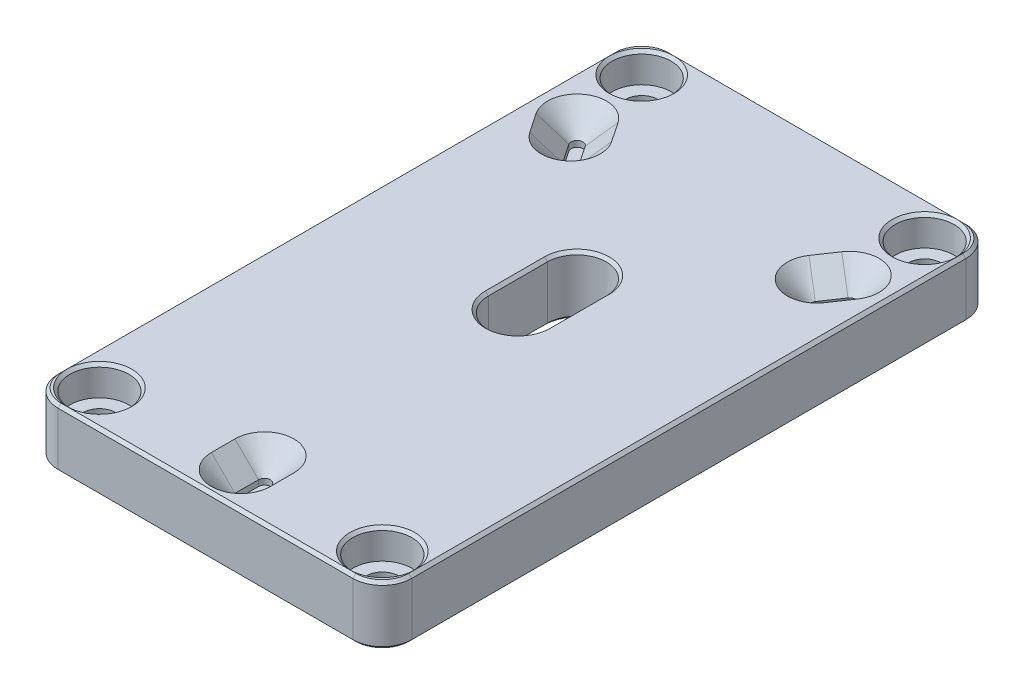
SolidWorks part; units mm, degrees
ref_plane "Front Plane" through (0, 0, 0) normal (0, 0, 1) x (1, 0, 0)
ref_plane "Top Plane" through (0, 0, 0) normal (0, 1, 0) x (1, 0, 0)
ref_plane "Right Plane" through (0, 0, 0) normal (1, 0, 0) x (0, 0, -1)
sketch "Sketch1" plane through (0, 0, 0) normal (0, 1, 0) x (1, 0, 0)
  line L1 (-30, 52) -> (30, 52)
  line L2 (-30, 52) -> (-30, -52)
  line L3 (-30, -52) -> (30, -52)
  line L4 (30, 52) -> (30, -52)
  line L5 (-30, 52) -> (30, -52) construction
  line L6 (-30, -52) -> (30, 52) construction
  point P0 (0, 0)
  dimension "D1" = 60
  dimension "D2" = 104
extrude "Boss-Extrude1" add sketch "Sketch1" along normal blind 10
sketch "Sketch10" plane through (0, 10, 0) normal (0, 1, 0) x (1, 0, 0)
  circle A0 centre (0, -44) radius 2.75 construction
  circle A1 centre (-22, 32.5) radius 2.75 construction
  circle A2 centre (22, 32.5) radius 2.75 construction
  circle A3 centre (0, -44) radius 2.75
  circle A4 centre (-22, 32.5) radius 2.75
  circle A5 centre (22, 32.5) radius 2.75
  circle A6 centre (0, 34) radius 15 construction
  circle A7 centre (0, -21.5) radius 15 construction
  circle A8 centre (0, 34) radius 15
  circle A9 centre (0, -21.5) radius 15
  circle A10 centre (0, 11) radius 1.85 construction
  circle A11 centre (0, 1) radius 1.85 construction
  circle A12 centre (0, 11) radius 1.85
  circle A13 centre (0, 1) radius 1.85
sketch "Sketch3" plane through (0, 10, 0) normal (0, 1, 0) x (1, 0, 0)
  line L0 (0, 0) -> (22, 32.5) construction
  line L1 (0, 0) -> (-22, 32.5) construction
  line L5 (0, 0) -> (0, -44) construction
  line L6 (-23.1211, 34.1562) -> (-20.8789, 30.8438) construction
  line L7 (-22.293, 34.7168) -> (-20.0508, 31.4043)
  line L8 (-23.9492, 33.5957) -> (-21.707, 30.2832)
  line L9 (23.1211, 34.1562) -> (20.8789, 30.8438) construction
  line L10 (23.9492, 33.5957) -> (21.707, 30.2832)
  line L11 (22.293, 34.7168) -> (20.0508, 31.4043)
  line L12 (0, -46) -> (0, -42) construction
  line L13 (-1, -46) -> (-1, -42)
  line L14 (1, -46) -> (1, -42)
  arc A0 (-22.293, 34.7168) -> (-23.9492, 33.5957) centre (-23.1211, 34.1562) ccw
  arc A1 (-21.707, 30.2832) -> (-20.0508, 31.4043) centre (-20.8789, 30.8438) ccw
  arc A2 (23.9492, 33.5957) -> (22.293, 34.7168) centre (23.1211, 34.1562) ccw
  arc A3 (20.0508, 31.4043) -> (21.707, 30.2832) centre (20.8789, 30.8438) ccw
  arc A4 (-1, -46) -> (1, -46) centre (0, -46) ccw
  arc A5 (1, -42) -> (-1, -42) centre (0, -42) ccw
  point P19 (-22, 32.5)
  point P25 (22, 32.5)
  point P32 (0, -44)
  dimension "D2" = 1
  dimension "D1" = 4
extrude "Cut-Extrude1" cut sketch "Sketch3" against normal blind 5
chamfer "Chamfer1" distance 4 angle 45 12 edges at (-22.8281, 10, -31.9394) (-20.3183, 10, -30.0157) (-23.6817, 10, -34.9843) (-21.1719, 10, -33.0606) (-1, 10, 44) (0, 10, 47) (0, 10, 41) (1, 10, 44) (21.1719, 10, -33.0606) (20.3183, 10, -30.0157) (23.6817, 10, -34.9843) (22.8281, 10, -31.9394)
sketch "Sketch5" plane through (0, 10, 0) normal (0, 1, 0) x (1, 0, 0)
  circle A2 centre (0, -21.5) radius 15 construction
  circle A3 centre (0, -21.5) radius 15
  circle A4 centre (0, 34) radius 15 construction
  circle A5 centre (0, 34) radius 15
extrude "Cut-Extrude3" cut sketch "Sketch5" against normal through all from offset 1.5 offset against normal yes
sketch "Sketch6" plane through (0, 10, 0) normal (0, 1, 0) x (1, 0, 0)
  line L8 (24, -46) -> (24, 46)
  line L9 (24, 46) -> (-24, 46)
  line L10 (-24, 46) -> (-24, -46)
  line L11 (-24, -46) -> (24, -46)
  line L12 (24, -46) -> (24, 46) construction
  line L13 (24, 46) -> (-24, 46) construction
  line L14 (-24, 46) -> (-24, -46) construction
  line L15 (-24, -46) -> (24, -46) construction
  dimension "D1" = 6
hole_wizard "CBORE for M5 SHCS1" positions "Sketch7" profile "Sketch8" counterbore size "M5" standard "ANSI Metric" end condition through all
sketch "Sketch7" plane through (0, 10, 0) normal (0, 1, 0) x (1, 0, 0)
  point P0 (-24, 46)
  point P3 (24, 46)
  point P6 (24, -46)
  point P9 (-24, -46)
sketch "Sketch8" plane through (-24, 10, -46) normal (1, 0, 0) x (0, 0, 1)
  line L0 (0, 0) -> (0, 10)
  line L1 (0, 10) -> (2.75, 10)
  line L3 (2.75, 10) -> (2.75, 5)
  line L4 (2.75, 5) -> (5, 5)
  line L5 (5, 5) -> (5, 0)
  line L7 (5, 0) -> (0, 0)
  line L11 (0, -6.35) -> (0, 107.95) construction
  dimension "Thru Hole Dia." = 5.5
  dimension "Thru Hole Depth" = 10
  dimension "C'Bore Dia." = 10
  dimension "C'Bore Depth" = 5
fillet "Fillet1" radius 5 4 edges at (30, 5, -52) (30, 5, 52) (-30, 5, 52) (-30, 5, -52)
sketch "Sketch9" plane through (0, 0, 0) normal (0, -1, 0) x (1, 0, 0)
  circle A0 centre (0, -19) radius 0.35
  circle A4 centre (0, -34) radius 15 construction
  dimension "D1" = 0.7
extrude "Boss-Extrude2" add sketch "Sketch9" against normal up to next
sketch "Sketch11" plane through (0, 0, 0) normal (0, -1, 0) x (1, 0, 0)
  circle A0 centre (0, 6.5) radius 0.35
  circle A1 centre (0, 21.5) radius 15 construction
  arc A2 (-0.35, -19.0041) -> (0.35, -19.0041) centre (0, -19) ccw construction
extrude "Boss-Extrude3" add sketch "Sketch11" against normal up to next contours A0
pattern_circular "CirPattern1" count 6 over 360 about axis through (0, 0, 21.5) along (0, 1, 0) of "Boss-Extrude3" reverse direction yes
pattern_circular "CirPattern2" count 6 over 360 about axis through (0, 0, -34) along (0, 1, 0) of "Boss-Extrude2" reverse direction yes
sketch "Sketch12" plane through (0, 10, 0) normal (0, 1, 0) x (1, 0, 0)
  line L0 (0, 1) -> (0, 11) construction
  line L1 (-5, 1) -> (-5, 11)
  line L2 (5, 1) -> (5, 11)
  arc A0 (-5, 1) -> (5, 1) centre (0, 1) ccw
  arc A1 (5, 11) -> (-5, 11) centre (0, 11) ccw
  point P4 (0, 6)
  dimension "D1" = 5
extrude "Cut-Extrude4" cut sketch "Sketch12" against normal through all
chamfer "Chamfer2" distance 0.5 angle 45 28 edges at (0, 0, 52) (28.5355, 0, 50.5355) (-28.5355, 0, 50.5355) (30, 0, 0) (-30, 0, 0) (28.5355, 0, -50.5355) (-28.5355, 0, -50.5355) (0, 0, -52) (-5, 0, -6) (0, 0, 4) (0, 0, -16) (5, 0, -6) (24, 10, 51) (-24, 10, 51) (-24, 10, -41) (24, 10, -41) (-5, 10, -6) (0, 10, 4) (0, 10, -16) (5, 10, -6) (-30, 10, 0) (-28.5355, 10, 50.5355) (-28.5355, 10, -50.5355) (0, 10, 52) (0, 10, -52) (28.5355, 10, 50.5355) (28.5355, 10, -50.5355) (30, 10, 0)
